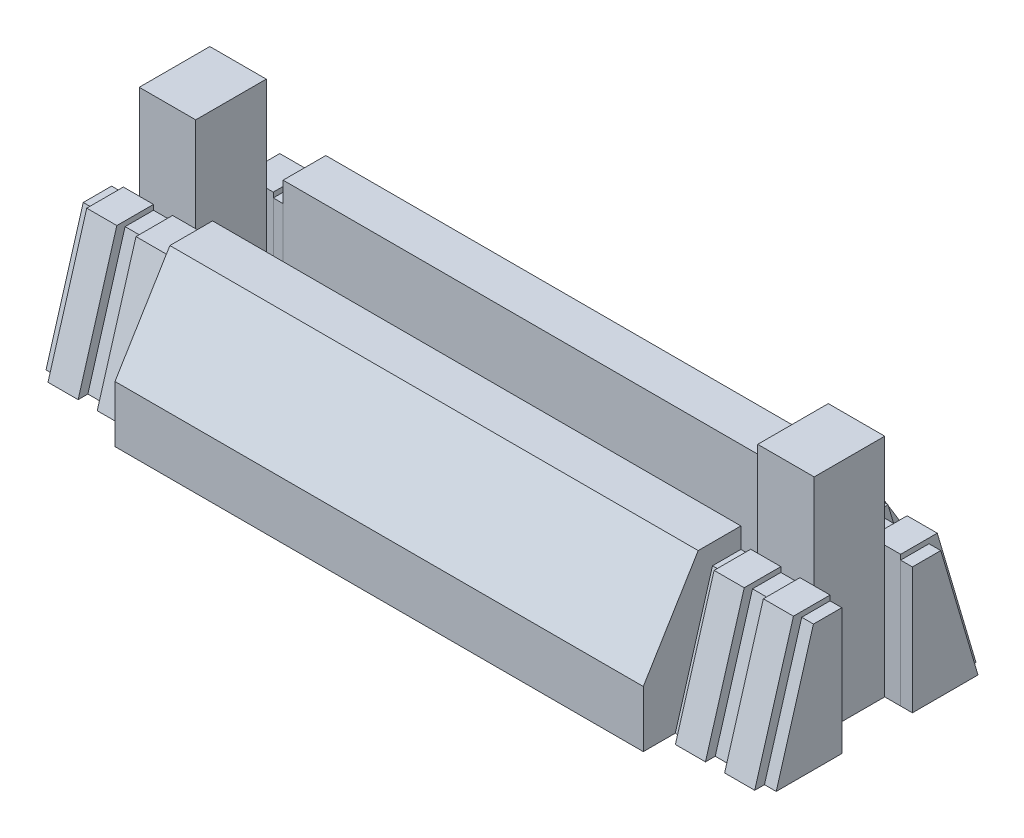
SolidWorks part; units mm, degrees
ref_plane "前视基准面" through (0, 0, 0) normal (0, 0, 1) x (1, 0, 0)
ref_plane "上视基准面" through (0, 0, 0) normal (0, 1, 0) x (1, 0, 0)
ref_plane "右视基准面" through (0, 0, 0) normal (1, 0, 0) x (0, 0, -1)
sketch "草图1" plane through (0, 0, 0) normal (1, 0, 0) x (0, 0, -1)
  line L0 (0, 24.7798) -> (0, -23.5091) construction
  line L1 (0, 0) -> (-232.46, 0)
  line L2 (-232.46, 0) -> (-100.52, 447.79)
  line L3 (-100.52, 447.79) -> (0, 447.79)
  line L4 (0, 447.79) -> (0, 0)
  line L5 (125, 638.6304) -> (125, -191.8876) construction
  line L6 (250, 447.79) -> (250, 0)
  line L7 (350.52, 447.79) -> (250, 447.79)
  line L8 (482.46, 0) -> (350.52, 447.79)
  line L9 (250, 0) -> (482.46, 0)
  dimension "D1" = 232.46
  dimension "D2" = 447.79
  dimension "D3" = 100.52
  dimension "D4" = 125
extrude "凸台-拉伸1" add sketch "草图1" along normal blind 41.66
sketch "草图2" plane through (41.66, 0, 0) normal (1, 0, 0) x (0, 0, -1)
  line L0 (0, 465.74) -> (-129.79, 465.74)
  line L1 (-129.79, 465.74) -> (-267.0189, 0)
  line L2 (-267.0189, 0) -> (0, 0)
  line L3 (0, 0) -> (0, 465.74)
  line L4 (-100.52, 447.79) -> (-232.46, 0) construction
  line L5 (125, 510.0964) -> (125, -27.4564) construction
  line L6 (250, 0) -> (250, 465.74)
  line L7 (517.0189, 0) -> (250, 0)
  line L8 (379.79, 465.74) -> (517.0189, 0)
  line L9 (250, 465.74) -> (379.79, 465.74)
  dimension "D1" = 129.79
  dimension "D2" = 465.74
  dimension "D3" = 125
extrude "凸台-拉伸2" add sketch "草图2" along normal blind 106.69
extrude "凸台-拉伸3" add sketch "草图1<2>" along normal blind 67.71 from surface starting at face at (148.35, 232.87, 99.2022)
sketch "草图1<2>" plane through (0, 0, 0) normal (1, 0, 0) x (0, 0, -1) same geometry as "草图1"
extrude "凸台-拉伸4" add sketch "草图2<2>" along normal blind 106.69 from surface starting at face at (216.06, 223.895, 83.245)
sketch "草图2<2>" plane through (41.66, 0, 0) normal (1, 0, 0) x (0, 0, -1) same geometry as "草图2"
extrude "凸台-拉伸5" add sketch "草图1<3>" along normal blind 34.9 from surface starting at face at (322.75, 232.87, 99.2022)
sketch "草图1<3>" plane through (0, 0, 0) normal (1, 0, 0) x (0, 0, -1) same geometry as "草图1"
sketch "草图3" plane through (357.65, 0, 0) normal (1, 0, 0) x (0, 0, -1)
  line L0 (0, 0) -> (0, 519.76)
  line L1 (0, 519.76) -> (-151.24, 519.76)
  line L2 (-151.24, 519.76) -> (-345.7242, 200)
  line L3 (-345.7242, 200) -> (-345.7242, 0)
  line L4 (-345.7242, 0) -> (0, 0)
  line L5 (125, 593.7437) -> (125, -171.1427) construction
  line L6 (595.7242, 0) -> (250, 0)
  line L7 (595.7242, 200) -> (595.7242, 0)
  line L8 (401.24, 519.76) -> (595.7242, 200)
  line L9 (250, 519.76) -> (401.24, 519.76)
  line L10 (250, 0) -> (250, 519.76)
  dimension "D1" = 519.76
  dimension "D2" = 151.24
  dimension "D3" = 374.26
  dimension "D4" = 200
  dimension "D5" = 125
extrude "凸台-拉伸6" add sketch "草图3" along normal blind 1871.94
ref_plane "基准面2" through (1293.62, 0, 0) normal (-1, 0, 0) x (0, 0, 1)
extrude "凸台-拉伸9" add sketch "草图1<4>" along normal blind 34.9 from surface starting at face at (2229.59, 247.904, 168.5377)
sketch "草图1<4>" plane through (0, 0, 0) normal (1, 0, 0) x (0, 0, -1) same geometry as "草图1"
extrude "凸台-拉伸10" add sketch "草图2<8>" along normal blind 106.69 from surface starting at face at (2264.49, 223.895, 83.245)
sketch "草图2<8>" plane through (41.66, 0, 0) normal (1, 0, 0) x (0, 0, -1) same geometry as "草图2"
extrude "凸台-拉伸11" add sketch "草图1<5>" along normal blind 67.71 from surface starting at face at (2371.18, 232.87, 99.2022)
sketch "草图1<5>" plane through (0, 0, 0) normal (1, 0, 0) x (0, 0, -1) same geometry as "草图1"
extrude "凸台-拉伸12" add sketch "草图2<10>" along normal blind 106.69 from surface starting at face at (2438.89, 223.895, 83.245)
sketch "草图2<10>" plane through (41.66, 0, 0) normal (1, 0, 0) x (0, 0, -1) same geometry as "草图2"
extrude "凸台-拉伸13" add sketch "草图1<6>" along normal blind 41.66 from surface starting at face at (2545.58, 232.87, 99.2022)
sketch "草图1<6>" plane through (0, 0, 0) normal (1, 0, 0) x (0, 0, -1) same geometry as "草图1"
sketch "草图4" plane through (0, 0, 0) normal (0, 1, 0) x (1, 0, 0)
  line L0 (148.35, 250) -> (41.66, 250) construction
  line L1 (98, 250) -> (298, 250)
  line L2 (98, 250) -> (98, 0)
  line L3 (98, 0) -> (298, 0)
  line L4 (298, 250) -> (298, 0)
  line L5 (322.75, 0) -> (216.06, 0) construction
  line L6 (0, 350.52) -> (0, 250) construction
  line L8 (1293.62, 250) -> (1293.62, 121.3156) construction
  line L9 (2289.24, 250) -> (2289.24, 0)
  line L10 (2489.24, 0) -> (2289.24, 0)
  line L11 (2489.24, 250) -> (2489.24, 0)
  line L12 (2489.24, 250) -> (2289.24, 250)
  line L13 (2587.24, 250) -> (2587.24, 350.52) construction
  dimension "D1" = 98
  dimension "D2" = 200
  dimension "D3" = 98
extrude "凸台-拉伸14" add sketch "草图4" along normal blind 800
